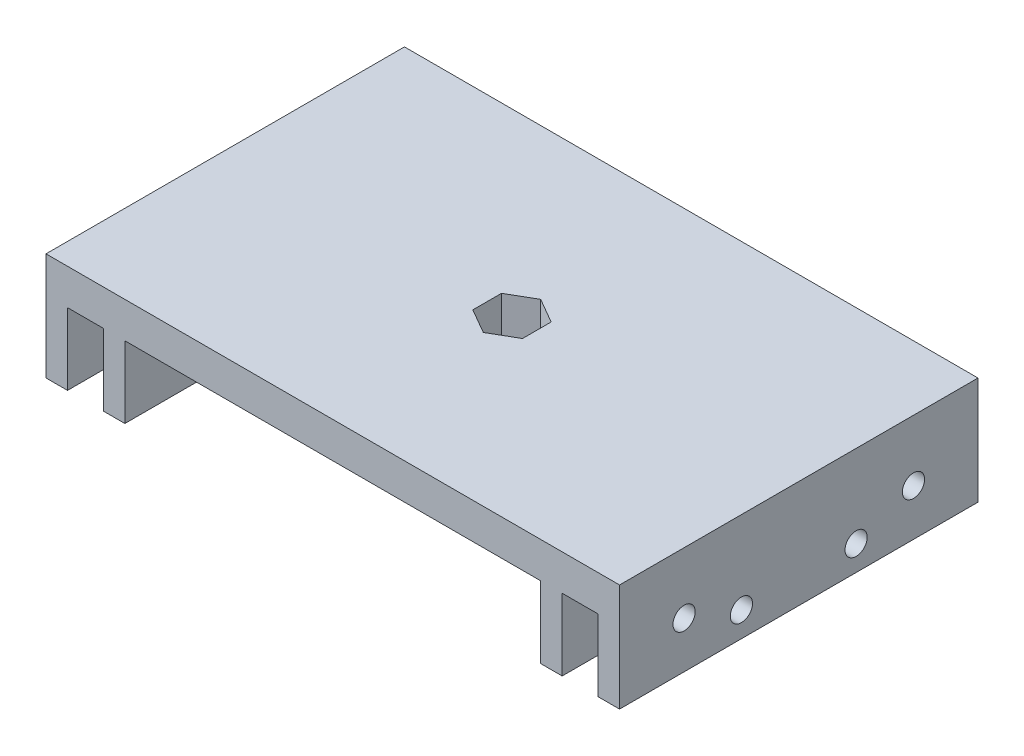
SolidWorks part; units mm, degrees
ref_plane "Front Plane" through (0, 0, 0) normal (0, 0, 1) x (1, 0, 0)
ref_plane "Top Plane" through (0, 0, 0) normal (0, 1, 0) x (1, 0, 0)
ref_plane "Right Plane" through (0, 0, 0) normal (1, 0, 0) x (0, 0, -1)
sketch "Sketch2" plane through (0, 0, 0) normal (0, 1, 0) x (1, 0, 0)
  circle A0 centre (0, 0) radius 9
extrude "Boss-Extrude1" add sketch "Sketch2" along normal blind 20
sketch "Sketch3" plane through (0, 20, 0) normal (0, 1, 0) x (1, 0, 0)
  line L0 (-3.4641, -2) -> (3.4641, 2) construction
  line L1 (0, -4) -> (0, 4) construction
  line L2 (3.4641, -2) -> (-3.4641, 2) construction
  line L15 (0, 4) -> (-3.4641, 2)
  line L16 (-3.4641, 2) -> (-3.4641, -2)
  line L17 (-3.4641, -2) -> (0, -4)
  line L18 (0, -4) -> (3.4641, -2)
  line L19 (3.4641, -2) -> (3.4641, 2)
  line L20 (3.4641, 2) -> (0, 4)
  circle A0 centre (0, 0) radius 4 construction
  point P4 (0, 0)
  point P5 (0, 0)
  point P6 (0, 0)
  point P9 (0, 0)
  point P10 (0, 0)
  point P11 (0, 0)
  point P14 (0, 0)
  point P15 (0, 0)
  point P17 (0, 0)
  point P20 (0, 0)
extrude "Cut-Extrude1" cut sketch "Sketch3" against normal blind 20
sketch "Sketch4" plane through (0, 20, 0) normal (0, 1, 0) x (1, 0, 0)
  line L1 (-40, 25) -> (40, 25)
  line L2 (-40, 25) -> (-40, -25)
  line L3 (-40, -25) -> (40, -25)
  line L4 (40, 25) -> (40, -25)
  line L5 (-40, 25) -> (40, -25) construction
  line L6 (-40, -25) -> (40, 25) construction
  circle A1 centre (0, 0) radius 4.5
extrude "Boss-Extrude3" add sketch "Sketch4" against normal blind 5
ref_plane "Plane3" through (0, 0, 0) normal (0.5, 0, -0.866) x (-0.866, 0, -0.5)
sketch "Sketch11" plane through (0, 0, 0) normal (0.5, 0, -0.866) x (-0.866, 0, -0.5)
  line L2 (0, 0) -> (0, 5) construction
  circle A0 centre (0, 5) radius 1.55
extrude "Cut-Extrude2" cut sketch "Sketch11" against normal blind 9 and the other way blind 9
ref_plane "Plane4" through (0, 0, 0) normal (-0.5, 0, -0.866) x (-0.866, 0, 0.5)
sketch "Sketch15" plane through (0, 0, 0) normal (-0.5, 0, -0.866) x (-0.866, 0, 0.5)
  line L0 (0, 0) -> (0, 9) construction
  circle A0 centre (0, 9) radius 1.55
extrude "Cut-Extrude9" cut sketch "Sketch15" against normal blind 9 and the other way blind 9
sketch "Sketch16" plane through (0, 15, 0) normal (0, -1, 0) x (1, 0, 0)
  line L0 (0, 0) -> (32, 0) construction
  line L6 (0, 0) -> (-32, 0) construction
  line L12 (-32, -25) -> (-32, 25)
  line L13 (-32, 25) -> (-29, 25)
  line L14 (-29, 25) -> (-29, -25)
  line L15 (-29, -25) -> (-32, -25)
  line L16 (-32, 0) -> (-37, 0) construction
  line L17 (-37, -25) -> (-37, 25)
  line L18 (-37, 25) -> (-40, 25)
  line L19 (-40, 25) -> (-40, -25)
  line L20 (-40, -25) -> (-37, -25)
  line L21 (32, -25) -> (32, 25)
  line L22 (32, 25) -> (29, 25)
  line L23 (29, 25) -> (29, -25)
  line L24 (29, -25) -> (32, -25)
  line L25 (32, 0) -> (37, 0) construction
  line L26 (37, -25) -> (37, 25)
  line L27 (37, 25) -> (40, 25)
  line L28 (40, 25) -> (40, -25)
  line L29 (40, -25) -> (37, -25)
  point P7 (-32, 0)
  point P14 (-37, 0)
  point P19 (32, 0)
  point P25 (37, 0)
extrude "Boss-Extrude4" add sketch "Sketch16" along normal blind 10
sketch "Sketch17" plane through (-40, 0, 0) normal (-1, 0, 0) x (0, 0, 1)
  line L0 (-25, 5) -> (-25, 8.5) construction
  line L1 (-25, 5) -> (-25, 20) construction
  line L2 (-25, 8.5) -> (-8, 8.5) construction
  line L3 (-8, 8.5) -> (8, 8.5) construction
  line L4 (-16, 11.5) -> (16, 11.5) construction
  line L5 (-25, 15) -> (-25, 11.5) construction
  line L6 (-25, 11.5) -> (-16, 11.5) construction
  circle A0 centre (-16, 11.5) radius 1.55
  circle A1 centre (-8, 8.5) radius 1.55
  circle A3 centre (8, 8.5) radius 1.55
  circle A5 centre (16, 11.5) radius 1.55
extrude "Cut-Extrude10" cut sketch "Sketch17" against normal up to surface (11 mm away) up to face at (-29, 10, 0)
sketch "Sketch18" plane through (40, 0, 0) normal (1, 0, 0) x (0, 0, -1)
  line L0 (-25, 5) -> (-25, 8.5) construction
  line L1 (-25, 8.5) -> (-8, 8.5) construction
  line L2 (-8, 8.5) -> (8, 8.5) construction
  line L3 (8, 8.5) -> (-8, 8.5) construction
  line L4 (-25, 15) -> (-25, 11.5) construction
  line L5 (-25, 5) -> (-25, 20) construction
  line L6 (-25, 11.5) -> (-16, 11.5) construction
  line L7 (-16, 11.5) -> (16, 11.5) construction
  line L8 (16, 11.5) -> (-16, 11.5) construction
  circle A0 centre (-8, 8.5) radius 1.55
  circle A1 centre (8, 8.5) radius 1.55
  circle A2 centre (16, 11.5) radius 1.55
  circle A3 centre (-16, 11.5) radius 1.55
extrude "Cut-Extrude11" cut sketch "Sketch18" against normal up to surface (11 mm away) up to face at (29, 10, 0)
sketch "Sketch19" plane through (0, 0, 0) normal (-0.5, 0, -0.866) x (-0.866, 0, 0.5)
  circle A0 centre (0, 9) radius 3.5
extrude "Cut-Extrude14" cut sketch "Sketch19" against normal blind 3 from offset 9 contours A0
extrude "Cut-Extrude15" cut sketch "Sketch19<3>" along normal blind 3 from offset 9 offset against normal yes
sketch "Sketch19<3>" plane through (0, 0, 0) normal (-0.5, 0, -0.866) x (-0.866, 0, 0.5) same geometry as "Sketch19"
sketch "Sketch20" plane through (0, 0, 0) normal (0.5, 0, -0.866) x (-0.866, 0, -0.5)
  circle A0 centre (0, 5) radius 3.5
extrude "Cut-Extrude16" cut sketch "Sketch20" against normal blind 3 from offset 9
extrude "Cut-Extrude17" cut sketch "Sketch20<2>" along normal blind 3 from offset 9 offset against normal yes
sketch "Sketch20<2>" plane through (0, 0, 0) normal (0.5, 0, -0.866) x (-0.866, 0, -0.5) same geometry as "Sketch20"
